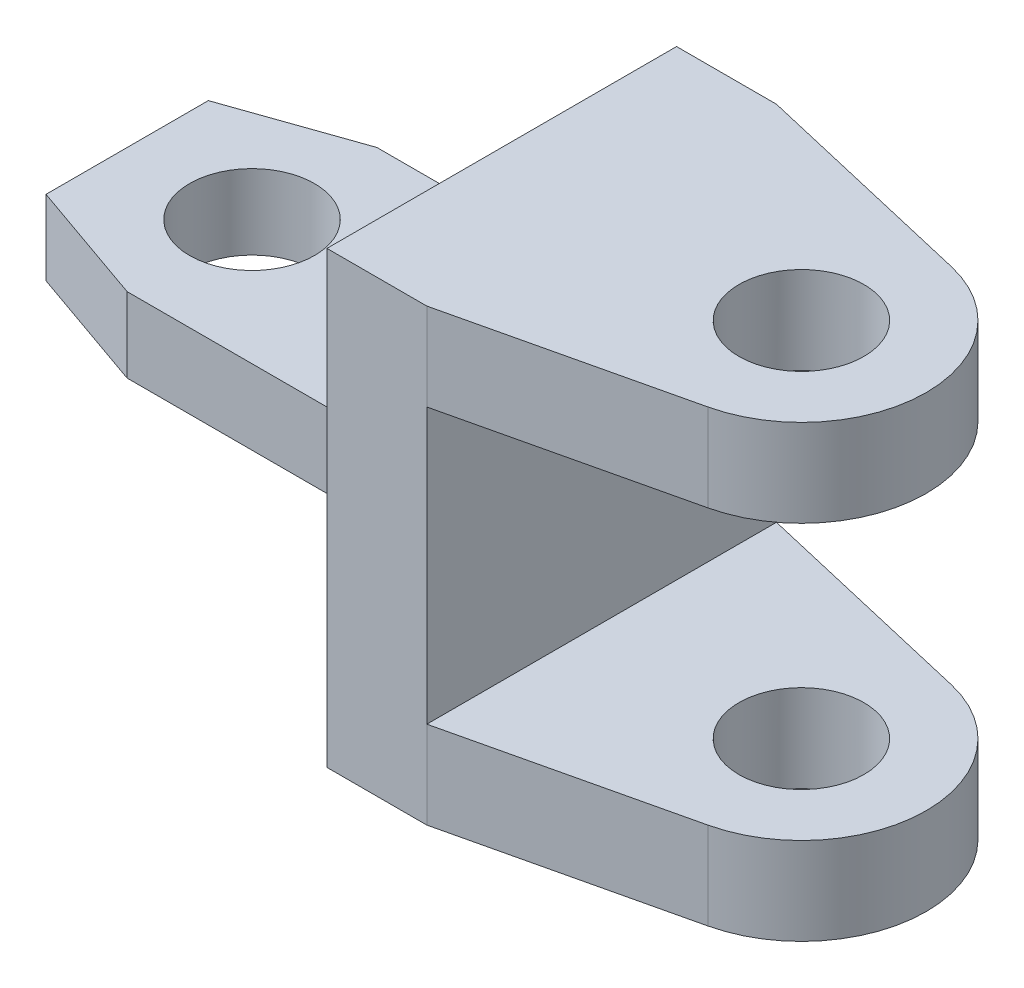
SolidWorks part; units mm, degrees
ref_plane "Front Plane" through (0, 0, 0) normal (0, 0, 1) x (1, 0, 0)
ref_plane "Top Plane" through (0, 0, 0) normal (0, 1, 0) x (1, 0, 0)
ref_plane "Right Plane" through (0, 0, 0) normal (1, 0, 0) x (0, 0, -1)
sketch "Sketch1" plane through (0, 0, 0) normal (0, 1, 0) x (1, 0, 0)
  line L4 (-26.9852, 0) -> (26.9852, 0) construction
  line L5 (-30, -6.5) -> (-30, 6.5)
  line L6 (-30, 6.5) -> (-20, 10)
  line L11 (-20, 10) -> (0, 10)
  line L12 (0, 10) -> (0, 14)
  line L13 (0, 14) -> (8, 14)
  line L17 (0, -14) -> (8, -14)
  line L18 (0, -10) -> (0, -14)
  line L19 (-20, -10) -> (0, -10)
  line L20 (-30, -6.5) -> (-20, -10)
  line L21 (0, 10) -> (0, -10)
  line L22 (8, 14) -> (26.2713, 9.7386)
  line L23 (8, -14) -> (26.2713, -9.7386)
  arc A0 (26.2713, -9.7386) -> (26.2713, 9.7386) centre (24, 0) ccw
  circle A1 centre (24, 0) radius 5
  circle A2 centre (-20, 0) radius 5
  circle A3 centre (-7, 0) radius 3
  point P3 (0, 0)
  point P17 (24, 0)
  point P22 (-30, 0)
  dimension "D8" = 10
  dimension "D9" = 10
  dimension "D10" = 6
  dimension "D13" = 10
  dimension "D1" = 13
  dimension "D2" = 20
  dimension "D3" = 20
  dimension "D4" = 28
  dimension "D5" = 24
  dimension "D6" = 8
  dimension "D7" = 30
  dimension "D11" = 7
  dimension "D12" = 20
extrude "Boss-Extrude3" add sketch "Sketch1" along normal blind 18 and the other way blind 18 contours L23 A0 L22 L13 L12 L21 A1 L18 L17 region at (13.7595, 0, 0)
extrude "Boss-Extrude4" add sketch "Sketch1<5>" along normal blind 3 and the other way blind 3 contours A2 A3 L21 L11 L6 L5 L20 L19 region at (-13.7454, 0, 0)
sketch "Sketch1<5>" plane through (0, 0, 0) normal (0, 1, 0) x (1, 0, 0) same geometry as "Sketch1"
sketch "Sketch3" plane through (0, 0, -14) normal (0, 0, -1) x (-1, 0, 0)
  line L0 (0, -18) -> (0, 18) construction
  line L1 (-8, 11) -> (-48.6531, 11)
  line L2 (-8, 11) -> (-8, -11)
  line L3 (-8, -11) -> (-48.6531, -11)
  line L4 (-48.6531, 11) -> (-48.6531, -11)
  point P6 (-48.6531, 0)
  dimension "D1" = 22
  dimension "D2" = 8
extrude "Cut-Extrude2" cut sketch "Sketch3" against normal through all
